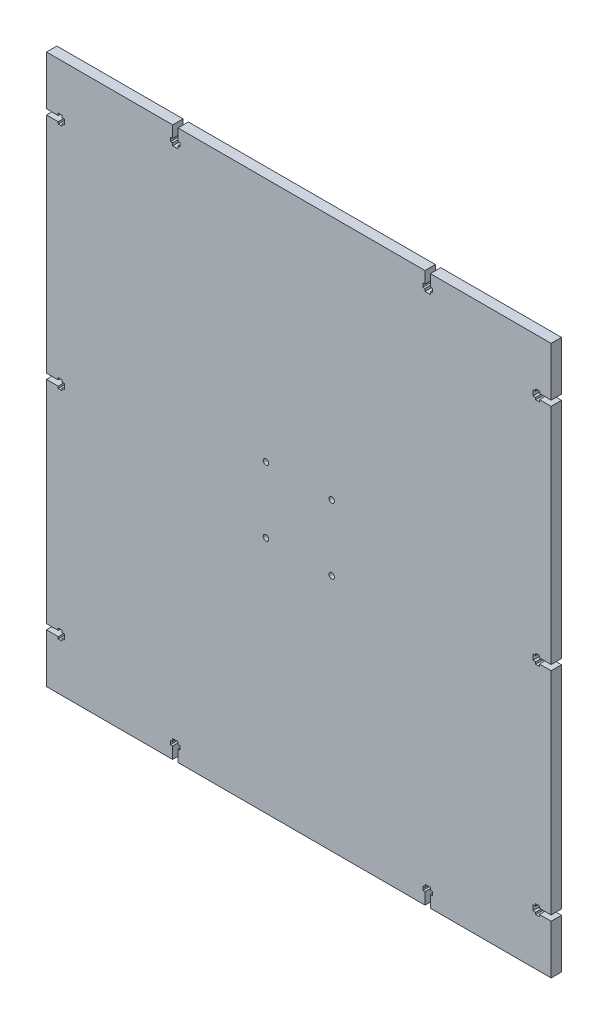
SolidWorks part; units mm, degrees
material "Клен"
ref_plane "Спереди" through (0, 0, 0) normal (0, 0, 1) x (1, 0, 0)
ref_plane "Сверху" through (0, 0, 0) normal (0, 1, 0) x (1, 0, 0)
ref_plane "Справа" through (0, 0, 0) normal (1, 0, 0) x (0, 0, -1)
sketch "Эскиз1" plane through (0, 0, 0) normal (0, 0, 1) x (1, 0, 0)
  line L1 (0, 0) -> (73, 0)
  line L2 (0, 0) -> (0, -28.45)
  line L3 (0, -318) -> (73, -318)
  line L4 (292, 0) -> (292, -28.45)
  line L15 (146, 38.6612) -> (146, -369.0135) construction
  line L16 (338.8892, -160.95) -> (-53.634, -160.95) construction
  line L17 (-48.9358, -30) -> (338.8892, -30) construction
  line L18 (-48.9358, -289.55) -> (329.134, -289.55) construction
  line L76 (0, -289.55) -> (0, -318)
  line L80 (73, 38.6612) -> (73, -369.0135) construction
  line L81 (219, 38.6612) -> (219, -369.0135) construction
  line L82 (76.1, 0) -> (219, 0)
  line L83 (222.1, 0) -> (292, 0)
  line L84 (76.1, -318) -> (219, -318)
  line L85 (222.1, -318) -> (292, -318)
  line L86 (338.8892, -28.45) -> (-48.9358, -28.45) construction
  line L87 (285.2, -28.45) -> (285.2, -27.25)
  line L88 (283, -32.75) -> (285.2, -32.75)
  line L89 (283, -28.45) -> (281.5, -28.45)
  line L90 (285.2, -27.25) -> (283, -27.25)
  line L91 (292, -28.45) -> (285.2, -28.45)
  line L92 (281.5, -31.55) -> (283, -31.55)
  line L93 (222.1, -6.8) -> (222.1, 0)
  line L94 (222.1, -9) -> (223.3, -9)
  line L95 (219, -10.5) -> (222.1, -10.5)
  line L96 (222.1, -10.5) -> (222.1, -9)
  line L97 (219, 0) -> (219, -6.8)
  line L98 (219, -6.8) -> (217.8, -6.8)
  line L99 (223.3, -9) -> (223.3, -6.8)
  line L100 (217.8, -6.8) -> (217.8, -9)
  line L101 (223.3, -6.8) -> (222.1, -6.8)
  line L102 (217.8, -9) -> (219, -9)
  line L103 (219, -9) -> (219, -10.5)
  line L104 (76.1, -6.8) -> (76.1, 0)
  line L105 (76.1, -9) -> (77.3, -9)
  line L106 (73, -10.5) -> (76.1, -10.5)
  line L107 (76.1, -10.5) -> (76.1, -9)
  line L108 (73, 0) -> (73, -6.8)
  line L109 (73, -6.8) -> (71.8, -6.8)
  line L110 (77.3, -9) -> (77.3, -6.8)
  line L111 (71.8, -6.8) -> (71.8, -9)
  line L112 (77.3, -6.8) -> (76.1, -6.8)
  line L113 (71.8, -9) -> (73, -9)
  line L114 (73, -9) -> (73, -10.5)
  line L115 (73, -309) -> (73, -307.5)
  line L116 (71.8, -309) -> (73, -309)
  line L117 (77.3, -311.2) -> (76.1, -311.2)
  line L118 (71.8, -311.2) -> (71.8, -309)
  line L119 (77.3, -309) -> (77.3, -311.2)
  line L120 (73, -311.2) -> (71.8, -311.2)
  line L121 (73, -318) -> (73, -311.2)
  line L122 (76.1, -307.5) -> (76.1, -309)
  line L123 (73, -307.5) -> (76.1, -307.5)
  line L124 (76.1, -309) -> (77.3, -309)
  line L125 (76.1, -311.2) -> (76.1, -318)
  line L126 (219, -309) -> (219, -307.5)
  line L127 (217.8, -309) -> (219, -309)
  line L128 (223.3, -311.2) -> (222.1, -311.2)
  line L129 (217.8, -311.2) -> (217.8, -309)
  line L130 (223.3, -309) -> (223.3, -311.2)
  line L131 (219, -311.2) -> (217.8, -311.2)
  line L132 (219, -318) -> (219, -311.2)
  line L133 (222.1, -307.5) -> (222.1, -309)
  line L134 (219, -307.5) -> (222.1, -307.5)
  line L135 (222.1, -309) -> (223.3, -309)
  line L136 (222.1, -311.2) -> (222.1, -318)
  line L137 (285.2, -32.75) -> (285.2, -31.55)
  line L138 (285.2, -31.55) -> (292, -31.55)
  line L139 (281.5, -28.45) -> (281.5, -31.55)
  line L140 (283, -27.25) -> (283, -28.45)
  line L141 (283, -31.55) -> (283, -32.75)
  line L142 (292, -33.1) -> (292, -31.55)
  line L143 (285.2, -286.45) -> (285.2, -285.25)
  line L144 (285.2, -289.55) -> (292, -289.55)
  line L145 (281.5, -286.45) -> (281.5, -289.55)
  line L146 (283, -285.25) -> (283, -286.45)
  line L147 (283, -286.45) -> (281.5, -286.45)
  line L148 (281.5, -289.55) -> (283, -289.55)
  line L149 (292, -286.45) -> (285.2, -286.45)
  line L150 (285.2, -285.25) -> (283, -285.25)
  line L151 (283, -289.55) -> (283, -290.75)
  line L152 (283, -290.75) -> (285.2, -290.75)
  line L153 (285.2, -290.75) -> (285.2, -289.55)
  line L155 (292, -289.55) -> (292, -318)
  line L157 (9, -31.55) -> (9, -32.75)
  line L158 (9, -27.25) -> (9, -28.45)
  line L159 (10.5, -28.45) -> (10.5, -31.55)
  line L160 (6.8, -31.55) -> (0, -31.55)
  line L161 (6.8, -32.75) -> (6.8, -31.55)
  line L162 (10.5, -31.55) -> (9, -31.55)
  line L163 (0, -28.45) -> (6.8, -28.45)
  line L164 (6.8, -27.25) -> (9, -27.25)
  line L165 (9, -28.45) -> (10.5, -28.45)
  line L166 (9, -32.75) -> (6.8, -32.75)
  line L167 (6.8, -28.45) -> (6.8, -27.25)
  line L179 (6.8, -290.75) -> (6.8, -289.55)
  line L180 (9, -290.75) -> (6.8, -290.75)
  line L181 (9, -289.55) -> (9, -290.75)
  line L182 (6.8, -285.25) -> (9, -285.25)
  line L183 (0, -286.45) -> (6.8, -286.45)
  line L184 (10.5, -289.55) -> (9, -289.55)
  line L185 (9, -286.45) -> (10.5, -286.45)
  line L186 (9, -285.25) -> (9, -286.45)
  line L187 (10.5, -286.45) -> (10.5, -289.55)
  line L188 (6.8, -289.55) -> (0, -289.55)
  line L189 (6.8, -286.45) -> (6.8, -285.25)
  line L191 (292, -33.1) -> (292, -160.95)
  line L192 (281.5, -160.95) -> (281.5, -164.05)
  line L193 (281.5, -164.05) -> (283, -164.05)
  line L194 (283, -160.95) -> (281.5, -160.95)
  line L195 (285.2, -164.05) -> (292, -164.05)
  line L196 (283, -165.25) -> (285.2, -165.25)
  line L197 (285.2, -165.25) -> (285.2, -164.05)
  line L198 (285.2, -159.75) -> (283, -159.75)
  line L199 (283, -159.75) -> (283, -160.95)
  line L200 (292, -160.95) -> (285.2, -160.95)
  line L201 (285.2, -160.95) -> (285.2, -159.75)
  line L202 (283, -164.05) -> (283, -165.25)
  line L203 (292, -164.05) -> (292, -286.45)
  line L204 (9, -164.05) -> (9, -165.25)
  line L205 (6.8, -160.95) -> (6.8, -159.75)
  line L206 (0, -160.95) -> (6.8, -160.95)
  line L207 (9, -159.75) -> (9, -160.95)
  line L208 (6.8, -159.75) -> (9, -159.75)
  line L209 (6.8, -165.25) -> (6.8, -164.05)
  line L210 (9, -165.25) -> (6.8, -165.25)
  line L211 (6.8, -164.05) -> (0, -164.05)
  line L212 (9, -160.95) -> (10.5, -160.95)
  line L213 (10.5, -164.05) -> (9, -164.05)
  line L214 (10.5, -160.95) -> (10.5, -164.05)
  line L215 (0, -31.55) -> (0, -160.95)
  line L216 (0, -286.45) -> (0, -164.05)
  line L217 (119.0367, -141.95) -> (174.301, -141.95) construction
  line L218 (165, -134.5429) -> (165, -158.0449) construction
  circle A0 centre (165, -141.95) radius 1.6
  circle A1 centre (127, -141.95) radius 1.6
  circle A2 centre (165, -179.95) radius 1.6
  circle A3 centre (127, -179.95) radius 1.6
  dimension "D11" = 3.2
  dimension "D1" = 292
  dimension "D2" = 318
  dimension "D3" = 30
  dimension "D4" = 73
  dimension "D5" = 73
  dimension "D6" = 28.45
  dimension "D7" = 28.45
  dimension "D8" = 160.95
  dimension "D9" = 19
  dimension "D10" = 19
extrude "Бобышка-Вытянуть1" add sketch "Эскиз1" along normal blind 6
